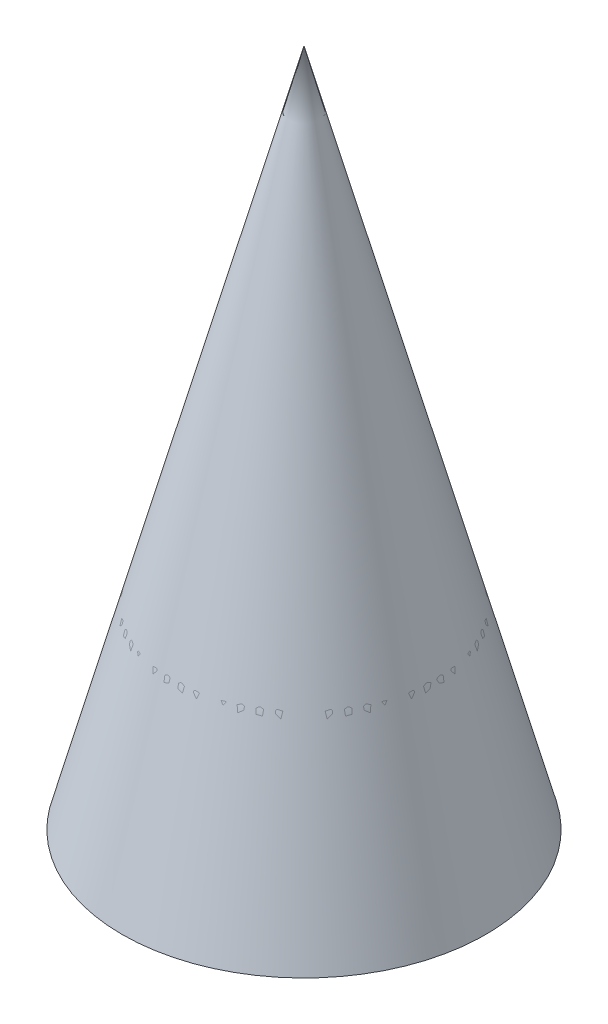
SolidWorks part; units mm, degrees
ref_plane "前视基准面" through (0, 0, 0) normal (0, 0, 1) x (1, 0, 0)
ref_plane "上视基准面" through (0, 0, 0) normal (0, 1, 0) x (1, 0, 0)
ref_plane "右视基准面" through (0, 0, 0) normal (1, 0, 0) x (0, 0, -1)
sketch "草图1" plane through (0, 0, 0) normal (0, 0, 1) x (1, 0, 0)
  line L0 (0, 0) -> (0, 150)
  line L1 (0, 150) -> (40.1924, 0)
  line L2 (40.1924, 0) -> (0, 0)
  line L3 (0, 118.336) -> (0, -13.1932) construction
  dimension "D1" = 15
  dimension "D2" = 150
revolve "旋转1" add sketch "草图1" angle 360 about L3
sketch "草图2" plane through (0, 0, 0) normal (0, 0, 1) x (1, 0, 0)
  line L1 (0, 107.0395) -> (0, 77.0495)
  line L2 (0, 150) -> (0, -1.036) construction
  line L3 (0, 64.0839) -> (0, 4.0939)
  arc A0 (0, 77.0495) -> (0, 107.0395) centre (0, 92.0445) ccw
  arc A1 (0, 4.0939) -> (0, 64.0839) centre (0, 34.0889) ccw
  point P3 (-26.3557, 135.9232)
  dimension "D1" = 29.99
  dimension "D2" = 59.99
  dimension "D3" = 57.9555
  dimension "D4" = 115.9111
revolve "切除-旋转1" cut sketch "草图2" angle 360 about L2
